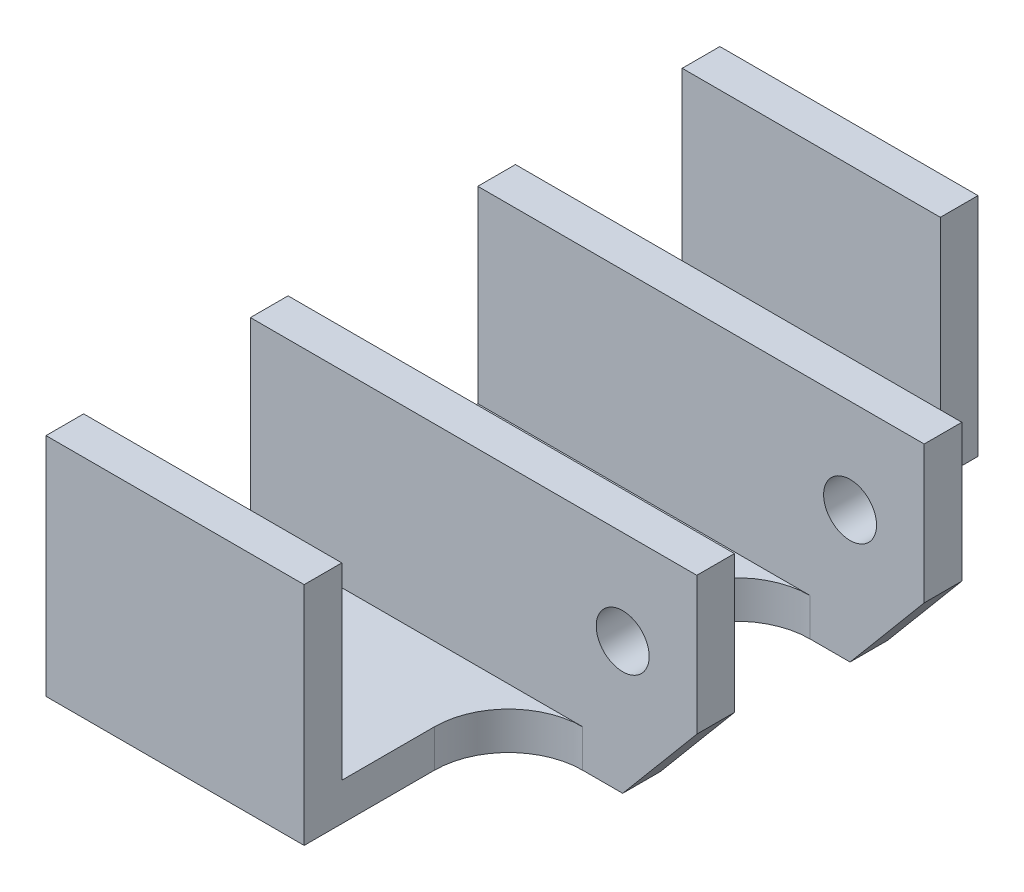
SolidWorks part; units mm, degrees
material "ABS"
ref_plane "Front" through (0, 0, 0) normal (0, 0, 1) x (1, 0, 0)
ref_plane "Top" through (0, 0, 0) normal (0, 1, 0) x (1, 0, 0)
ref_plane "Right" through (0, 0, 0) normal (1, 0, 0) x (0, 0, -1)
ref_axis "Axis1" through (0, 0, 55) along (0, 0, -1)
sketch "Sketch2" plane through (0, 0, 0) normal (1, 0, 0) x (0, 0, -1)
  line L0 (0, 0) -> (0, 195.4886) construction
  line L1 (-12.8, 0) -> (0, 0)
  line L2 (-12.8, 0) -> (-12.8, 25.4)
  line L3 (-12.8, 25.4) -> (-17.88, 25.4)
  line L4 (-17.88, 25.4) -> (-17.88, 0)
  line L5 (-17.88, 0) -> (-40.38, 0)
  line L6 (-40.38, 0) -> (-40.38, 25.4)
  line L7 (-15.34, -5.08) -> (0, -5.08)
  line L8 (-15.34, -5.08) -> (-15.34, -5.08)
  line L9 (-15.34, -5.08) -> (-15.34, -5.08)
  line L10 (-15.34, -5.08) -> (-15.34, -5.08)
  line L11 (-15.34, -5.08) -> (-45.46, -5.08)
  line L12 (-45.46, -5.08) -> (-45.46, 25.4)
  line L13 (-45.46, 25.4) -> (-40.38, 25.4)
  line L14 (0, 0) -> (0, -5.08)
  line L15 (45.46, 25.4) -> (40.38, 25.4)
  line L16 (45.46, -5.08) -> (45.46, 25.4)
  line L17 (15.34, -5.08) -> (45.46, -5.08)
  line L18 (15.34, -5.08) -> (0, -5.08)
  line L19 (40.38, 0) -> (40.38, 25.4)
  line L20 (17.88, 0) -> (40.38, 0)
  line L21 (17.88, 25.4) -> (17.88, 0)
  line L22 (12.8, 25.4) -> (17.88, 25.4)
  line L23 (12.8, 0) -> (12.8, 25.4)
  line L24 (12.8, 0) -> (0, 0)
  dimension "D1" = 25.4
  dimension "D2" = 12.8
  dimension "D3" = 22.5
  dimension "D4" = 5.08
  dimension "D5" = 5.08
extrude "Boss-Extrude1" add sketch "Sketch2" along normal blind 34.83 contours L23 L24 L14 L18 L17 L16 L15 L19 L20 L21 L22 | L14 L1 L2 L3 L4 L5 L6 L13 L12 L11 L7 region at (0, -0.5473, 6.4) region at (0, -0.5473, -6.4)
sketch "Sketch3" plane through (34.83, 0, 0) normal (1, 0, 0) x (0, 0, -1)
  line L0 (45.46, -5.08) -> (-45.46, -5.08) construction
  line L1 (-17.88, 25.4) -> (-12.8, 25.4)
  line L2 (-17.88, 25.4) -> (-17.88, -5.08)
  line L3 (-17.88, -5.08) -> (-12.8, -5.08)
  line L4 (-12.8, 25.4) -> (-12.8, -5.08)
  line L5 (-12.8, 0) -> (-12.8, 25.4) construction
  line L6 (17.88, 25.4) -> (17.88, 0) construction
  line L7 (12.8, 25.4) -> (17.88, 25.4)
  line L8 (12.8, 25.4) -> (12.8, -5.08)
  line L9 (12.8, -5.08) -> (17.88, -5.08)
  line L10 (17.88, 25.4) -> (17.88, -5.08)
extrude "Boss-Extrude2" add sketch "Sketch3" along normal blind 25.4
hole_wizard "1/4 Clearance Hole1" positions "Sketch4" profile "Sketch6" hole size "1/4" standard "ANSI Inch" end condition through all
sketch "Sketch4" plane through (0, 0, 17.88) normal (0, 0, 1) x (1, 0, 0)
  line L0 (60.23, 25.4) -> (60.23, -5.08) construction
  line L1 (60.23, 25.4) -> (0, 25.4) construction
  point P0 (50.23, 12.7)
  dimension "D1" = 10
  dimension "D2" = 12.7
sketch "Sketch6" plane through (50.23, 12.7, 17.88) normal (1, 0, 0) x (0, -1, 0)
  line L0 (0, 0) -> (0, 63.34)
  line L1 (0, 63.34) -> (3.5712, 63.34)
  line L2 (3.5712, 63.34) -> (3.5712, 0)
  line L5 (3.5712, 0) -> (0, 0)
  line L11 (0, -6.35) -> (0, 107.95) construction
  dimension "Thru Hole Dia." = 7.1425
  dimension "Thru Hole Depth" = 63.34
chamfer "Chamfer1" distance 10 angle 50 2 edges at (60.23, -5.08, -15.34) (60.23, -5.08, 15.34) first distance on face at (37.4917, -5.08, 0)
fillet "Fillet1" radius 10 4 edges at (34.83, -2.54, -12.8) (34.83, -2.54, -17.88) (34.83, -2.54, 12.8) (34.83, -2.54, 17.88)
hole_wizard "1/4 Clearance Hole2" positions "Sketch7" profile "Sketch8" hole size "1/4" standard "ANSI Inch" end condition through all
sketch "Sketch7" plane through (0, -5.08, 0) normal (0, -1, 0) x (-1, 0, 0)
  line L0 (0, 0) -> (-34.83, 0) construction
  line L1 (0, 45.46) -> (0, -45.46) construction
  line L2 (-34.83, 2.8) -> (-34.83, -2.8) construction
  point P0 (-17.415, 0)
sketch "Sketch8" plane through (17.415, -5.08, 0) normal (1, 0, 0) x (0, 0, -1)
  line L0 (0, 0) -> (0, 30.48)
  line L1 (0, 30.48) -> (3.5712, 30.48)
  line L2 (3.5712, 30.48) -> (3.5712, 0)
  line L5 (3.5712, 0) -> (0, 0)
  line L11 (0, -6.35) -> (0, 107.95) construction
  dimension "Thru Hole Dia." = 7.1425
  dimension "Thru Hole Depth" = 30.48
sketch "Sketch1" plane through (0, 0, 0) normal (0, 1, 0) x (1, 0, 0)
  line L0 (-65.6184, 0) -> (65.6184, 0) construction
  line L1 (-17.5, 30.734) -> (17.5, 30.734)
  line L2 (17.5, 30.734) -> (17.5, 52.734)
  line L3 (17.5, 52.734) -> (-17.5, 52.734)
  line L4 (-17.5, 52.734) -> (-17.5, 30.734)
  line L5 (0, 52.734) -> (0, 0) construction
  point P4 (0, 0)
  dimension "D1" = 35
  dimension "D2" = 22
  dimension "D3" = 61.468
